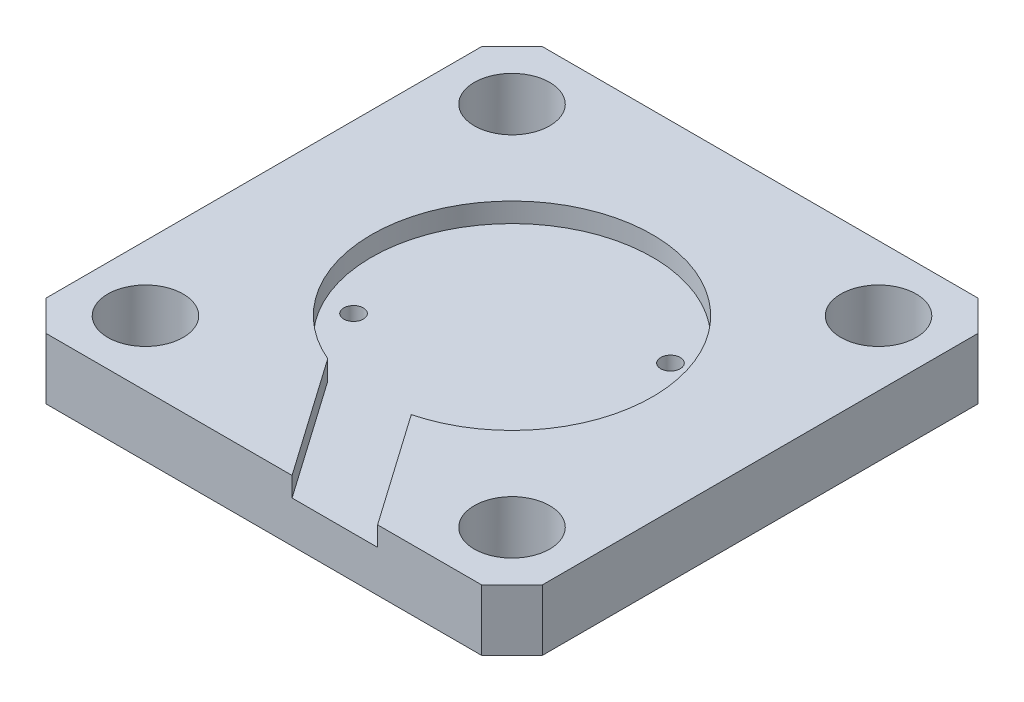
SolidWorks part; units mm, degrees
ref_plane "Front Plane" through (0, 0, 0) normal (0, 0, 1) x (1, 0, 0)
ref_plane "Top Plane" through (0, 0, 0) normal (0, 1, 0) x (1, 0, 0)
ref_plane "Right Plane" through (0, 0, 0) normal (1, 0, 0) x (0, 0, -1)
sketch "Sketch1" plane through (0, 0, 0) normal (0, 1, 0) x (1, 0, 0)
  line L1 (-20.32, -20.32) -> (20.32, -20.32)
  line L2 (-20.32, -20.32) -> (-20.32, 20.32)
  line L3 (-20.32, 20.32) -> (20.32, 20.32)
  line L4 (20.32, -20.32) -> (20.32, 20.32)
  line L5 (-20.32, -20.32) -> (20.32, 20.32) construction
  line L6 (-20.32, 20.32) -> (20.32, -20.32) construction
  point P0 (0, 0)
  dimension "D1" = 40.64
  dimension "D2" = 40.64
extrude "Boss-Extrude1" add sketch "Sketch1" along normal blind 5
sketch "Sketch2" plane through (0, 5, 0) normal (0, 1, 0) x (1, 0, 0)
  line L1 (-15, -15) -> (15, -15) construction
  line L2 (-15, -15) -> (-15, 15) construction
  line L3 (-15, 15) -> (15, 15) construction
  line L4 (15, -15) -> (15, 15) construction
  line L5 (-15, -15) -> (15, 15) construction
  line L6 (-15, 15) -> (15, -15) construction
  circle A0 centre (-15, 15) radius 3.085
  circle A1 centre (15, 15) radius 3.085
  circle A2 centre (15, -15) radius 3.085
  circle A3 centre (-15, -15) radius 3.085
  point P0 (0, 0)
  dimension "D3" = 6.17
  dimension "D1" = 30
  dimension "D2" = 30
  dimension "D4" = 2
  dimension "D5" = 2
extrude "Cut-Extrude1" cut sketch "Sketch2" against normal up to next contours A0 | A1 | A2 | A3
chamfer "Chamfer1" distance 2.5 angle 45 4 edges at (-20.32, 2.5, 20.32) (20.32, 2.5, 20.32) (20.32, 2.5, -20.32) (-20.32, 2.5, -20.32)
sketch "Sketch3" plane through (0, 5, 0) normal (0, 1, 0) x (1, 0, 0)
  circle A0 centre (0, 0) radius 11.5
  dimension "D1" = 23
extrude "Cut-Extrude2" cut sketch "Sketch3" against normal blind 1.6
ref_point "Point1"
sketch "Sketch4" plane through (0, 5, 0) normal (0, 1, 0) x (1, 0, 0)
  circle A0 centre (0, 0) radius 12000
  circle A1 centre (0, 0) radius 15.5
  circle A2 centre (0, 0) radius 11.925
  dimension "D1" = 24000
  dimension "D2" = 31
  dimension "D3" = 23.85
extrude "Cut-Extrude3" [suppressed] cut sketch "Sketch4" against normal blind 2.6 contours A1 A2
sketch "Sketch5" plane through (0, 3.4, 0) normal (0, 1, 0) x (1, 0, 0)
  line L0 (0, 0) -> (0, -11.5) construction
  line L1 (-1, -9.5) -> (1, -9.5) construction
  line L2 (-1, -11.5) -> (1, -11.5) construction
  line L3 (-1, -11.5) -> (-1, -7.5) construction
  line L4 (-1, -7.5) -> (1, -7.5) construction
  line L5 (1, -11.5) -> (1, -7.5) construction
  line L6 (-1, -11.5) -> (1, -7.5) construction
  line L7 (-1, -7.5) -> (1, -11.5) construction
  line L8 (-1, -7.8) -> (1, -7.8)
  line L9 (-1, -11.2) -> (1, -11.2)
  circle A0 centre (0, 0) radius 11.5 construction
  circle A1 centre (0, 0) radius 9.5 construction
  arc A2 (-1, -7.8) -> (-1, -11.2) centre (-1, -9.5) ccw
  arc A7 (1, -11.2) -> (1, -7.8) centre (1, -9.5) ccw
  point P6 (0, -9.5)
  point P14 (0, -9.5)
  dimension "D1" = 4
  dimension "D2" = 2
  dimension "D3" = 0
  dimension "D4" = 3.4
extrude "Cut-Extrude4" [suppressed] cut sketch "Sketch5" against normal through all contours L9 A7 L8 A2
sketch "Sketch6" plane through (0, 5, 0) normal (0, 1, 0) x (1, 0, 0)
  line L8 (-20.32, 17.82) -> (-20.32, -17.82)
  line L9 (-20.32, 17.82) -> (-20.32, -17.82)
  line L10 (-20.32, -17.82) -> (-17.82, -20.32)
  line L11 (-20.32, -17.82) -> (-17.82, -20.32)
  line L12 (-17.82, -20.32) -> (17.82, -20.32)
  line L13 (-17.82, -20.32) -> (17.82, -20.32)
  line L14 (17.82, -20.32) -> (20.32, -17.82)
  line L15 (17.82, -20.32) -> (20.32, -17.82)
  line L16 (20.32, -17.82) -> (20.32, 17.82)
  line L17 (20.32, -17.82) -> (20.32, 17.82)
  line L18 (20.32, 17.82) -> (17.82, 20.32)
  line L19 (20.32, 17.82) -> (17.82, 20.32)
  line L20 (17.82, 20.32) -> (-17.82, 20.32)
  line L21 (17.82, 20.32) -> (-17.82, 20.32)
  line L22 (-17.82, 20.32) -> (-20.32, 17.82)
  line L23 (-17.82, 20.32) -> (-20.32, 17.82)
  circle A3 centre (0, 0) radius 11.5 construction
  circle A4 centre (0, 0) radius 11.5
  dimension "D1" = 0
extrude "Cut-Extrude5" [suppressed] cut sketch "Sketch6" against normal blind 1
sketch "Sketch7" plane through (0, 3.4, 0) normal (0, 1, 0) x (1, 0, 0)
  line L0 (8.2431, 4.7273) -> (-8.2431, -4.7273) construction
  circle A0 centre (8.2431, 4.7273) radius 0.8
  circle A1 centre (0, 0) radius 11.5
  circle A2 centre (0, 0) radius 11.5 construction
  circle A3 centre (8.2431, 4.7273) radius 1
  circle A4 centre (8.2431, 4.7273) radius 1 construction
  circle A5 centre (-8.2431, -4.7273) radius 1
  circle A6 centre (-8.2431, -4.7273) radius 1 construction
  circle A7 centre (0, 0) radius 11
  circle A8 centre (0, 0) radius 11 construction
  circle A9 centre (-8.2431, -4.7273) radius 0.8
  dimension "D5" = 1.6
  dimension "D6" = 1.6
  dimension "D1" = 0
  dimension "D2" = 0
  dimension "D3" = 0
  dimension "D4" = 0
extrude "Cut-Extrude6" cut sketch "Sketch7" against normal through all contours A9 | A0 | A0 region at (8.2431, 3.4, -4.7273) region at (-8.2431, 3.4, 4.7273)
sketch "Sketch8" plane through (0, 5, 0) normal (0, 1, 0) x (1, 0, 0)
  line L0 (-5.9882, -8.4546) -> (-1.2912, -5.1657)
  line L1 (2.32, -20.32) -> (9.32, -20.32)
  line L2 (9.32, -20.32) -> (-8.7925, 5.5474)
  line L3 (2.32, -20.32) -> (-14.076, 3.0959)
  line L8 (-20.32, 17.82) -> (-20.32, -17.82)
  line L9 (-20.32, -17.82) -> (-17.82, -20.32)
  line L10 (-17.82, -20.32) -> (17.82, -20.32)
  line L11 (17.82, -20.32) -> (20.32, -17.82)
  line L12 (20.32, -17.82) -> (20.32, 17.82)
  line L13 (20.32, 17.82) -> (17.82, 20.32)
  line L14 (17.82, 20.32) -> (-17.82, 20.32)
  line L15 (-17.82, 20.32) -> (-20.32, 17.82)
  line L16 (-20.32, 17.82) -> (-20.32, -17.82)
  line L17 (-20.32, -17.82) -> (-17.82, -20.32)
  line L18 (-17.82, -20.32) -> (17.82, -20.32)
  line L19 (17.82, -20.32) -> (20.32, -17.82)
  line L20 (20.32, -17.82) -> (20.32, 17.82)
  line L21 (20.32, 17.82) -> (17.82, 20.32)
  line L22 (17.82, 20.32) -> (-17.82, 20.32)
  line L23 (-17.82, 20.32) -> (-20.32, 17.82)
  circle M10 centre (0, 0) radius 11.5
  line M17 (-17.82, -20.32) -> (17.82, -20.32)
  dimension "D2" = 55
  dimension "D3" = 55
  dimension "D4" = 7
  dimension "D5" = 11
  dimension "D6" = 18.5
  dimension "D1" = 0
extrude "Cut-Extrude7" cut sketch "Sketch8" against normal up to surface (1.6 mm away) contours L3 L2 M17 M10 region at (2.6311, 5, 15.8033) up to face at (-8.2431, 3.4, 5.5273)
fillet "Fillet1" [suppressed] radius 3.125
